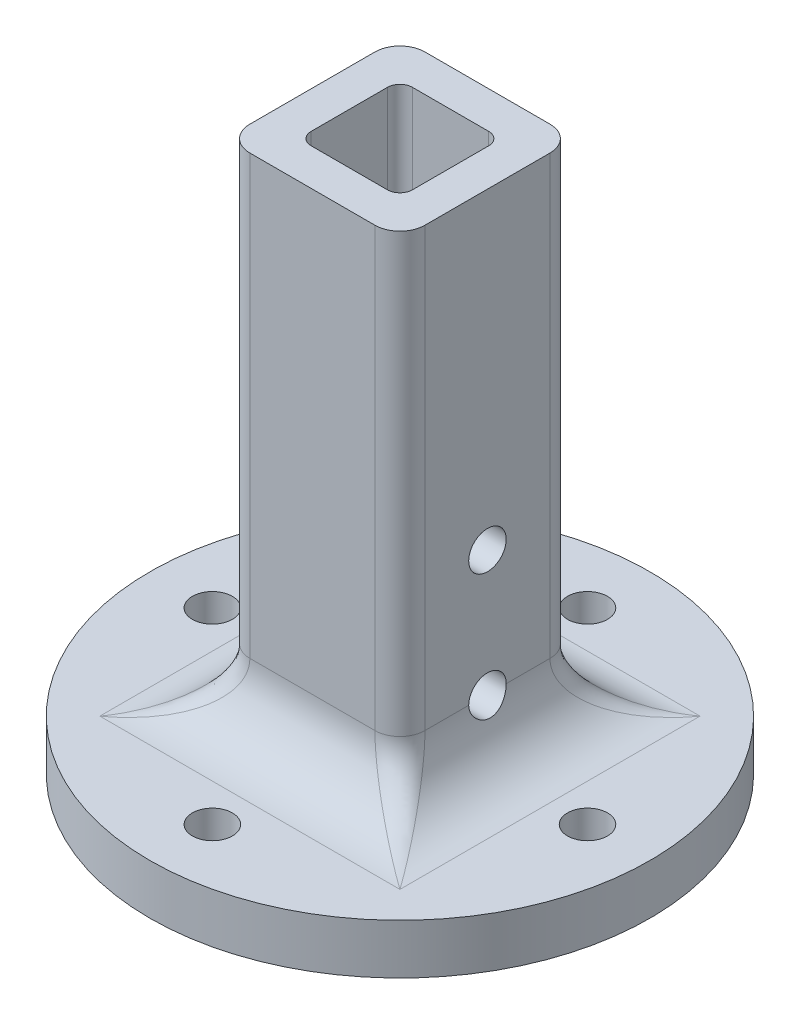
SolidWorks part; units mm, degrees
ref_plane "前视基准面" through (0, 0, 0) normal (0, 0, 1) x (1, 0, 0)
ref_plane "上视基准面" through (0, 0, 0) normal (0, 1, 0) x (1, 0, 0)
ref_plane "右视基准面" through (0, 0, 0) normal (1, 0, 0) x (0, 0, -1)
sketch "草图1" plane through (0, 0, 0) normal (0, 1, 0) x (1, 0, 0)
  line L0 (0, 0) -> (0, 20) construction
  line L1 (0, 0) -> (-20, 0) construction
  circle A0 centre (0, 0) radius 20
  circle A1 centre (0, 15) radius 1.6
  circle A2 centre (-15, 0) radius 1.6
  circle A4 centre (15, 0) radius 1.6
  circle A5 centre (0, -15) radius 1.6
  dimension "D1" = 40
  dimension "D2" = 15
  dimension "D3" = 15
extrude "凸台-拉伸1" add sketch "草图1" along normal blind 4
sketch "草图2" plane through (0, 4, 0) normal (0, 1, 0) x (1, 0, 0)
  line L0 (0, 0) -> (-14.1421, 14.1421) construction
  line L1 (0, 0) -> (14.1421, 14.1421) construction
  line L2 (0, 0) -> (-20, 0) construction
  line L3 (0, 0) -> (0, 20) construction
  line L5 (-4.05, -4.05) -> (4.05, -4.05)
  line L6 (-4.05, -4.05) -> (-4.05, 4.05)
  line L7 (-4.05, 4.05) -> (4.05, 4.05)
  line L8 (4.05, -4.05) -> (4.05, 4.05)
  line L9 (-7, -7) -> (7, -7)
  line L10 (-7, -7) -> (-7, 7)
  line L11 (-7, 7) -> (7, 7)
  line L12 (7, -7) -> (7, 7)
  dimension "D1" = 8.1
  dimension "D2" = 14
  dimension "D3" = 7
  dimension "D4" = 4.05
extrude "凸台-拉伸2" add sketch "草图2" along normal blind 40
sketch "草图3" plane through (0, 0, 0) normal (1, 0, 0) x (0, 0, -1)
  line L3 (0, 4) -> (0, 26.3515) construction
  circle A5 centre (0, 19) radius 1.5
  circle A6 centre (0, 9) radius 1.5
  dimension "D6" = 3
extrude "切除-拉伸1" cut sketch "草图3" against normal through all and the other way through all
fillet "圆角1" radius 5 4 edges at (-7, 4, 0) (0, 4, -7) (7, 4, 0) (0, 4, 7)
fillet "圆角2" radius 2 8 edges at (-8.4645, 5.4645, -8.4645) (8.4645, 5.4645, -8.4645) (8.4645, 5.4645, 8.4645) (-8.4645, 5.4645, 8.4645) (-7, 26.5, -7) (7, 26.5, -7) (7, 26.5, 7) (-7, 26.5, 7)
fillet "圆角3" radius 1 4 edges at (4.05, 24, 4.05) (-4.05, 24, 4.05) (4.05, 24, -4.05) (-4.05, 24, -4.05)
